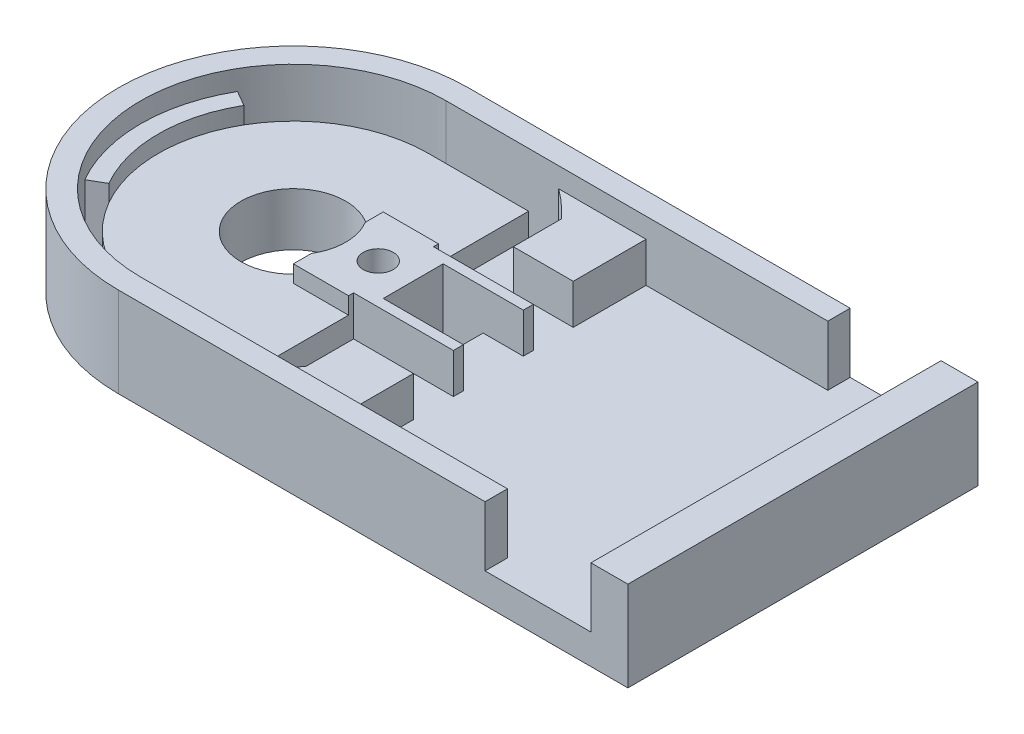
SolidWorks part; units mm, degrees
note: The reader was unsure of these and kept them because the rebuilt part matched: shared geometry of "Sketch11<5>".
ref_plane "Front Plane" through (0, 0, 0) normal (0, 0, 1) x (1, 0, 0)
ref_plane "Top Plane" through (0, 0, 0) normal (0, 1, 0) x (1, 0, 0)
ref_plane "Right Plane" through (0, 0, 0) normal (1, 0, 0) x (0, 0, -1)
sketch "Sensor Body Base Sketch" plane through (0, 0, 0) normal (0, 1, 0) x (1, 0, 0)
  line L1 (0, 17.5294) -> (51.025, 17.5294)
  line L2 (51.025, 17.5294) -> (51.025, -17.5294)
  line L3 (51.025, -17.5294) -> (0, -17.5294)
  arc A0 (0, 17.5294) -> (0, -17.5294) centre (0, 0) ccw
  dimension "D1" = 35.0589
  dimension "D2" = 51.025
extrude "Sensor Body Base" add sketch "Sensor Body Base Sketch" along normal blind 9
sketch "Camera Hole Sketch" plane through (0, 9, 0) normal (0, 1, 0) x (1, 0, 0)
  circle A0 centre (0, 0) radius 5.25
  dimension "D1" = 10.5
extrude "Camera Hole" cut sketch "Camera Hole Sketch" against normal through all
sketch "Cover Plate Cutout Sketch" plane through (0, 9, 0) normal (0, 1, 0) x (1, 0, 0)
  line L0 (-55, 0) -> (55, 0) construction
  line L1 (0, 15.29) -> (51.025, 15.29)
  line L3 (0, -15.29) -> (51.025, -15.29)
  line L4 (51.025, 15.29) -> (51.025, -15.29)
  line L5 (3.9355, 3) -> (10.7266, 3)
  line L7 (3.9355, -3) -> (10.7266, -3)
  line L8 (10.7266, 3) -> (10.7266, -3)
  line L9 (51.025, 15.29) -> (47.325, 15.29)
  line L10 (51.025, 15.29) -> (51.025, 5.29)
  line L12 (47.325, 15.29) -> (47.325, 5.29)
  line L14 (47.325, -15.29) -> (47.325, -5.29)
  line L15 (51.025, -15.29) -> (47.325, -15.29)
  line L16 (51.025, -15.29) -> (51.025, -5.29)
  line L17 (47.325, 5.29) -> (47.325, -5.29)
  line L18 (51.025, 5.29) -> (51.025, -5.29)
  arc A0 (0, 15.29) -> (0, -15.29) centre (0, 0) ccw
  arc A1 (3.9355, -3) -> (3.9355, 3) centre (0, 0) ccw
  circle M5 centre (0, 0) radius 5.25
  dimension "D1" = 51.025
  dimension "D2" = 6
  dimension "D3" = 10
  dimension "D4" = 3.7
  dimension "D5" = 15.29
extrude "Cover Plate Cutout" cut sketch "Cover Plate Cutout Sketch" against normal blind 2 contours L1 A0 L3 L14 L17 L12 L5 L8 L7 M5 | L8 L5 L7 M5
sketch "LED Driver Cutout Sketch" plane through (0, 7, 0) normal (0, 1, 0) x (1, 0, 0)
  line L0 (36.725, -17.5294) -> (47.325, -17.5294)
  line L1 (47.325, -17.5294) -> (47.325, 17.5294)
  line L2 (47.325, 17.5294) -> (38.225, 17.5294)
  line L3 (38.225, 17.5294) -> (38.225, 15.29)
  line L4 (38.225, 15.29) -> (20.025, 15.29)
  line L5 (20.025, 15.29) -> (20.025, -15.29)
  line L6 (20.025, -15.29) -> (36.725, -15.29)
  line L7 (36.725, -15.29) -> (36.725, -17.5294)
  line L13 (51.025, 17.5294) -> (0, 17.5294) construction
  line L14 (0, -17.5294) -> (51.025, -17.5294) construction
  point P10 (47.325, 0)
  point P18 (20.025, 0)
  dimension "D1" = 27.3
  dimension "D2" = 10.6
  dimension "D3" = 9.1
  dimension "D4" = 30.58
extrude "LED Driver Cutout" cut sketch "LED Driver Cutout Sketch" against normal blind 4 and the other way through all
sketch "Cover Plate Fastener Sketch" plane through (0, 0, 0) normal (0, 0, 1) x (1, 0, 0)
  line L0 (8.5, 7) -> (8.5, 3.214)
  line L1 (8.5, 3.214) -> (10, 4.08)
  line L2 (10, 4.08) -> (10, 7)
  line L3 (10, 7) -> (8.5, 7)
  line L4 (5.25, 7) -> (-5.25, 7) construction
  dimension "D1" = 60
  dimension "D2" = 8.5
  dimension "D3" = 1.5
  dimension "D4" = 2.92
revolve "Cover Plate Fastener" cut sketch "Cover Plate Fastener Sketch" angle 360 about L0
sketch "Lead Cutout Shared Sketch" plane through (0, 7, 0) normal (0, 1, 0) x (1, 0, 0)
  line L0 (0, 0) -> (-13.8819, -8.0147)
  line L1 (0, -13.5294) -> (14.025, -13.5294)
  line L2 (0, -13.5294) -> (0, -16.0294) construction
  line L3 (0, -16.0294) -> (14.025, -16.0294)
  line L4 (14.025, -13.5294) -> (14.025, -16.0294)
  line L5 (0, -17.5294) -> (36.725, -17.5294) construction
  line L7 (0, 0) -> (0, -13.5294) construction
  line L10 (14.025, -13.5294) -> (14.025, -8)
  line L11 (14.025, -8) -> (20.025, -8)
  line L12 (20.025, 15.29) -> (20.025, -15.29) construction
  line L13 (20.025, -8) -> (20.025, -4)
  line L15 (20.025, -4) -> (10.025, -4)
  line L16 (10.025, -4) -> (10.025, -13.5294)
  arc A2 (-13.8819, -8.0147) -> (0, -16.0294) centre (0, 0) ccw
  arc A3 (-11.7168, -6.7647) -> (0, -13.5294) centre (0, 0) ccw
  arc A4 (10.2009, -16.0294) -> (14.025, -12.8179) centre (0, 0) ccw
  line M50 (20.025, -15.29) -> (20.025, 15.29)
  dimension "D8" = 38
  dimension "D1" = 6
  dimension "D2" = 4
  dimension "D3" = 4
  dimension "D4" = 2.5
  dimension "D5" = 1.5
  dimension "D6" = 4
  dimension "D7" = 60
extrude "Lead Cutout" cut sketch "Lead Cutout Shared Sketch" against normal up to surface (7 mm away) and the other way through all
extrude "Folded Lead Cutout" cut sketch "Sketch11<5>" against normal up to surface (4 mm away) contours L15 L16 L1 L10 L11 M50
sketch "Sketch11<5>" plane through (0, 7, 0) normal (0, 1, 0) x (1, 0, 0) same geometry as "Lead Cutout Shared Sketch"
mirror "Lead Cutout Mirror" about plane through (0, 0, 0) normal (0, 0, 1) of "Lead Cutout", "Folded Lead Cutout"
sketch "Green Lead Cutout Sketch" plane through (0, 7, 0) normal (0, 1, 0) x (1, 0, 0)
  line L1 (16, -3) -> (12, -3)
  line L2 (16, -3) -> (16, 3)
  line L3 (16, 3) -> (12, 3)
  line L4 (12, -3) -> (12, 3)
  line L5 (16, -3) -> (12, 3) construction
  line L6 (16, 3) -> (12, -3) construction
  point P0 (14, 0)
  dimension "D1" = 12
  dimension "D2" = 6
  dimension "D3" = 4
extrude "Green Lead Cutout" cut sketch "Green Lead Cutout Sketch" against normal through all
sketch "Folded Green Lead Cutout Sketch" plane through (0, 7, 0) normal (0, 1, 0) x (1, 0, 0)
  line L0 (16, -3) -> (16, 3) construction
  line L1 (20.025, 3) -> (16, 3)
  line L2 (20.025, 3) -> (20.025, -3)
  line L3 (20.025, -3) -> (16, -3)
  line L4 (16, 3) -> (16, -3)
  line L5 (20.025, 3) -> (16, -3) construction
  line L6 (20.025, -3) -> (16, 3) construction
  line L8 (20.025, 4) -> (20.025, -4) construction
  point P0 (18.0125, 0)
  dimension "D1" = 6
extrude "Folded Green Lead Cutout" cut sketch "Folded Green Lead Cutout Sketch" against normal up to surface (4 mm away) up to face at (22.1631, 3, 0)
sketch "Camera PCB Cutout Sketch" plane through (0, 7, 0) normal (0, 1, 0) x (1, 0, 0)
  line L2 (0, 15.29) -> (10.025, 15.29)
  line L3 (10.025, 15.29) -> (10.025, 4.5)
  line L5 (4.5, 4.5) -> (10.025, 4.5)
  line L6 (-4.5, 4.5) -> (4.5, 4.5)
  line L7 (-4.5, 4.5) -> (-4.5, -4.5)
  line L8 (-4.5, -4.5) -> (4.5, -4.5)
  line L9 (4.5, 4.5) -> (4.5, -4.5)
  line L10 (4.5, -4.5) -> (10.025, -4.5)
  line L11 (10.025, -4) -> (10.025, -13.5294) construction
  line L12 (10.025, -4.5) -> (10.025, -15.29)
  line L13 (0, -15.29) -> (10.025, -15.29)
  arc A0 (0, 15.29) -> (0, -15.29) centre (0, 0) ccw
  arc M16 (-13.2415, 7.645) -> (-13.2415, -7.645) centre (0, 0) ccw
  line M19 (0, -13.5294) -> (10.025, -13.5294)
  line M20 (10.025, -13.5294) -> (10.025, -4)
  circle M31 centre (0, 0) radius 5.25
  line M93 (-13.2415, -7.645) -> (-11.7168, -6.7647)
  arc M94 (-11.7168, -6.7647) -> (0, -13.5294) centre (0, 0) ccw
  line M96 (10.025, 4) -> (10.025, 13.5294)
  line M97 (10.025, 13.5294) -> (0, 13.5294)
  arc M98 (0, 13.5294) -> (-11.7168, 6.7647) centre (0, 0) ccw
  line M99 (-11.7168, 6.7647) -> (-13.2415, 7.645)
  dimension "D5" = 15.29
  dimension "D1" = 9
  dimension "D2" = 10.79
  dimension "D3" = 5.525
  dimension "D4" = 5.525
  dimension "D6" = 10.025
  dimension "D7" = 10.025
extrude "Camera PCB Cutout" cut sketch "Camera PCB Cutout Sketch" against normal offset from surface (1.69 mm away) 5.31 contours L10 L8 L7 L6 L5 M31 M96 M97 M98 M99 M16 M93 M94 M19 M20 | L9 L8 M31 | L7 L8 M31 | L6 L7 M31 | L9 L6 M31 up to face at (14, 0, 0)
sketch "Cover Plate Support Sketch" plane through (0, 5.31, 0) normal (0, 1, 0) x (1, 0, 0)
  line L0 (-11.7168, 6.7647) -> (-13.2415, 7.645)
  line L1 (-11.7168, -6.7647) -> (-13.2415, -7.645)
  arc A0 (-13.2415, 7.645) -> (-13.2415, -7.645) centre (0, 0) ccw
  arc A1 (-11.7168, 6.7647) -> (-11.7168, -6.7647) centre (0, 0) ccw
  arc A5 (0, 15.29) -> (0, -15.29) centre (0, 0) ccw construction
  point P4 (-13.5294, 0)
  point P5 (-15.29, 0)
  dimension "D1" = 13.5294
  dimension "D2" = 60
extrude "Cover Plate Support" add sketch "Cover Plate Support Sketch" along normal up to surface (1.69 mm away) up to face at (15.8878, 7, 11.893)
